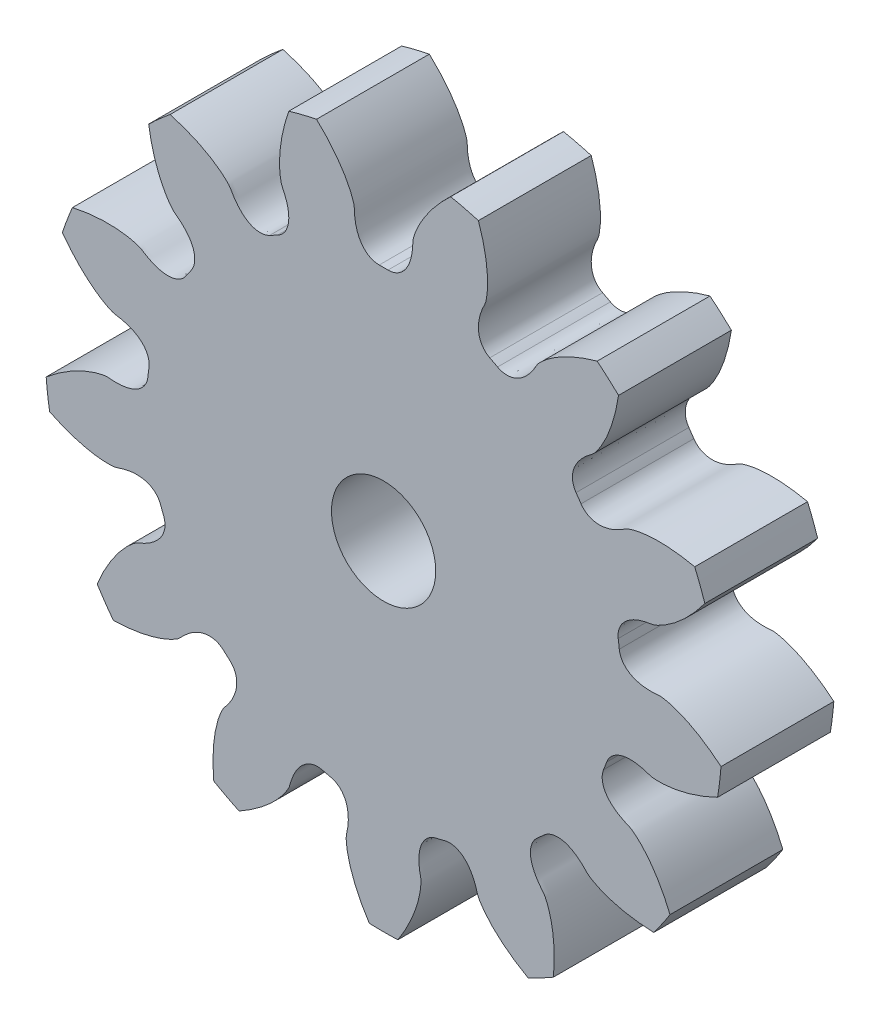
SolidWorks part; units mm, degrees
ref_plane "Front Plane" through (0, 0, 0) normal (0, 0, 1) x (1, 0, 0)
ref_plane "Top Plane" through (0, 0, 0) normal (0, 1, 0) x (1, 0, 0)
ref_plane "Right Plane" through (0, 0, 0) normal (1, 0, 0) x (0, 0, -1)
ref_axis "Axis1" through (0, 0, -88.99) along (0, 0, 1)
sketch "Gear-BaseSketch" plane through (0, 0, 0) normal (0, 0, 1) x (1, 0, 0)
  circle A0 centre (0, 0) radius 19.05
  dimension "D1" = 38.1
extrude "Non-standard pitches, 1.3000in P.D." add sketch "Gear-BaseSketch" along normal mid plane 6.35
sketch "Tooth-Sketch; Backlash: 0.0000in" plane through (0, 0, 0) normal (0, 0, 1) x (1, 0, 0)
  line L0 (0, 0) -> (0, 23.2715) construction
  arc A0 (-3.8481, 18.7422) -> (3.8481, 18.7422) centre (0, 0) cw
  arc A1 (-0.2469, 13.3327) -> (0.2469, 13.3327) centre (0, 0) cw
  spline S0 degree 3 poles (-3.8481, 18.7422) (-3.7218, 18.6231) (-3.478, 18.393) (-3.1459, 18.0393) (-2.8536, 17.6984) (-2.6002, 17.372) (-2.3833, 17.0633) (-2.2008, 16.7749) (-2.05, 16.5093) (-1.9283, 16.2688) (-1.8331, 16.0556) (-1.7608, 15.8716) (-1.71, 15.7183) (-1.6299, 15.4535) (-1.6449, 15.1831) (-1.6133, 14.9199) (-1.5946, 14.7948) (-1.5639, 14.635) (-1.5147, 14.4435) (-1.4363, 14.2255) (-1.3369, 14.0209) (-1.2124, 13.8297) (-1.0567, 13.654) (-0.862, 13.5004) (-0.6238, 13.3833) (-0.4097, 13.3382) (-0.2814, 13.3339) (-0.2469, 13.3327) knots 0 0 0 0 0.076117 0.146985 0.212603 0.272972 0.328091 0.377961 0.422581 0.461952 0.496073 0.524945 0.548568 0.566941 0.645853 0.664795 0.683262 0.701286 0.736155 0.769796 0.802733 0.835673 0.869515 0.905271 0.943737 0.984874 1 1 1 1
  spline S1 degree 3 poles (3.8481, 18.7422) (3.7218, 18.6231) (3.478, 18.393) (3.1459, 18.0393) (2.8536, 17.6984) (2.6002, 17.372) (2.3833, 17.0633) (2.2008, 16.7749) (2.05, 16.5093) (1.9283, 16.2688) (1.8331, 16.0556) (1.7608, 15.8716) (1.71, 15.7183) (1.6299, 15.4535) (1.6449, 15.1831) (1.6133, 14.9199) (1.5946, 14.7948) (1.5639, 14.635) (1.5147, 14.4435) (1.4363, 14.2255) (1.3369, 14.0209) (1.2124, 13.8297) (1.0567, 13.654) (0.862, 13.5004) (0.6238, 13.3833) (0.4097, 13.3382) (0.2814, 13.3339) (0.2469, 13.3327) knots 0 0 0 0 0.076117 0.146985 0.212603 0.272972 0.328091 0.377961 0.422581 0.461952 0.496073 0.524945 0.548568 0.566941 0.645853 0.664795 0.683262 0.701286 0.736155 0.769796 0.802733 0.835673 0.869515 0.905271 0.943737 0.984874 1 1 1 1
extrude "Tooth-Cut, D.P.=10.0000, P.A.=20.000deg" cut sketch "Tooth-Sketch; Backlash: 0.0000in" against normal through all and the other way through all
pattern_circular "Tooth Pattern, 13 / 13" count 13 over 360 about axis through (0, 0, -88.99) along (0, 0, 1) of "Tooth-Cut, D.P.=10.0000, P.A.=20.000deg"
sketch "Sketch1" plane through (0, 0, 3.175) normal (0, 0, 1) x (1, 0, 0)
  circle A0 centre (0, 0) radius 2.9337
  dimension "D1" = 5.8674
extrude "Extrude1" cut sketch "Sketch1" against normal through all
